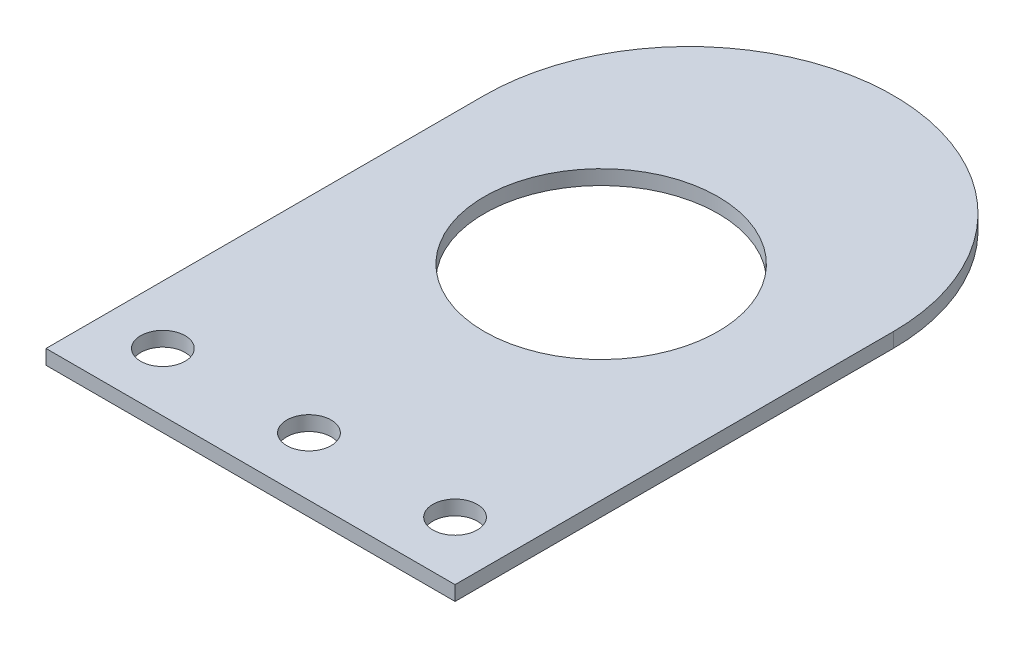
SolidWorks part; units mm, degrees
ref_plane "Front Plane" through (0, 0, 0) normal (0, 0, 1) x (1, 0, 0)
ref_plane "Top Plane" through (0, 0, 0) normal (0, 1, 0) x (1, 0, 0)
ref_plane "Right Plane" through (0, 0, 0) normal (1, 0, 0) x (0, 0, -1)
sketch "Sketch1" plane through (0, 0, 0) normal (0, 1, 0) x (1, 0, 0)
  line L0 (-22.225, 0) -> (-22.225, -47.625)
  line L1 (-22.225, -47.625) -> (22.225, -47.625)
  line L2 (22.225, -47.625) -> (22.225, 0)
  line L3 (0, 22.225) -> (0, -47.625) construction
  arc A0 (22.225, 0) -> (-22.225, 0) centre (0, 0) ccw
  circle A1 centre (0, -9.525) radius 12.7
  dimension "D1" = 25.4
  dimension "D3" = 44.45
  dimension "D4" = 69.85
  dimension "D2" = 38.1
base flange "Base-Flange1" sketch "Sketch1" thickness 1.5875 reverse thickness direction no parameters "D1"=254
sketch "Sketch12" plane through (0, -1.5875, 0) normal (0, -1, 0) x (1, 0, 0)
  line L0 (22.225, 47.625) -> (22.225, 0) construction
  line L1 (-22.225, 0) -> (-22.225, 47.625) construction
  line L2 (-22.225, 47.625) -> (22.225, 47.625) construction
  circle A0 centre (15.875, 41.275) radius 2.413
  circle A1 centre (0, 41.275) radius 2.413
  circle A2 centre (-15.875, 41.275) radius 2.413
  dimension "D1" = 6.35
  dimension "D5" = 4.826
  dimension "D2" = 6.35
  dimension "D3" = 22.225
  dimension "D4" = 6.35
extrude "Cut-Extrude1" cut sketch "Sketch12" against normal through all normal cut yes
sketch "Bend-Lines1" [suppressed] plane through (0, 0, 0) normal (0, 1, 0) x (1, 0, 0)
sketch "Bounding-Box1" [suppressed] plane through (0, 0, 0) normal (0, 1, 0) x (1, 0, 0)
sheet metal parameters "Sheet-Metal1" thickness 1.5875 parameters "D1"=254
flat pattern "Flat-Pattern1" [suppressed]
sketch "Bend-Lines2" plane through (0, 0, 0) normal (0, 1, 0) x (1, 0, 0)
sketch3d "Bounding-Box2" [suppressed]
  line L0 (22.225, 22.225, 0) -> (22.225, -47.625, 0) construction
  line L1 (-22.225, 22.225, 0) -> (-22.225, -47.625, 0) construction
  line L2 (22.225, 22.225, 0) -> (-22.225, 22.225, 0) construction
  line L3 (22.225, -47.625, 0) -> (-22.225, -47.625, 0) construction
sheet metal parameters "Sheet-Metal3" thickness 1.5875 parameters "D1"=254
flat pattern "Flat-Pattern1"
sketch "Bend-Lines2" plane through (0, 0, 0) normal (0, 1, 0) x (1, 0, 0)
sketch3d "Bounding-Box2" [suppressed]
  line L0 (-22.225, 22.225, 0) -> (-22.225, -47.625, 0) construction
  line L1 (22.225, 22.225, 0) -> (22.225, -47.625, 0) construction
  line L2 (-22.225, 22.225, 0) -> (22.225, 22.225, 0) construction
  line L3 (-22.225, -47.625, 0) -> (22.225, -47.625, 0) construction
